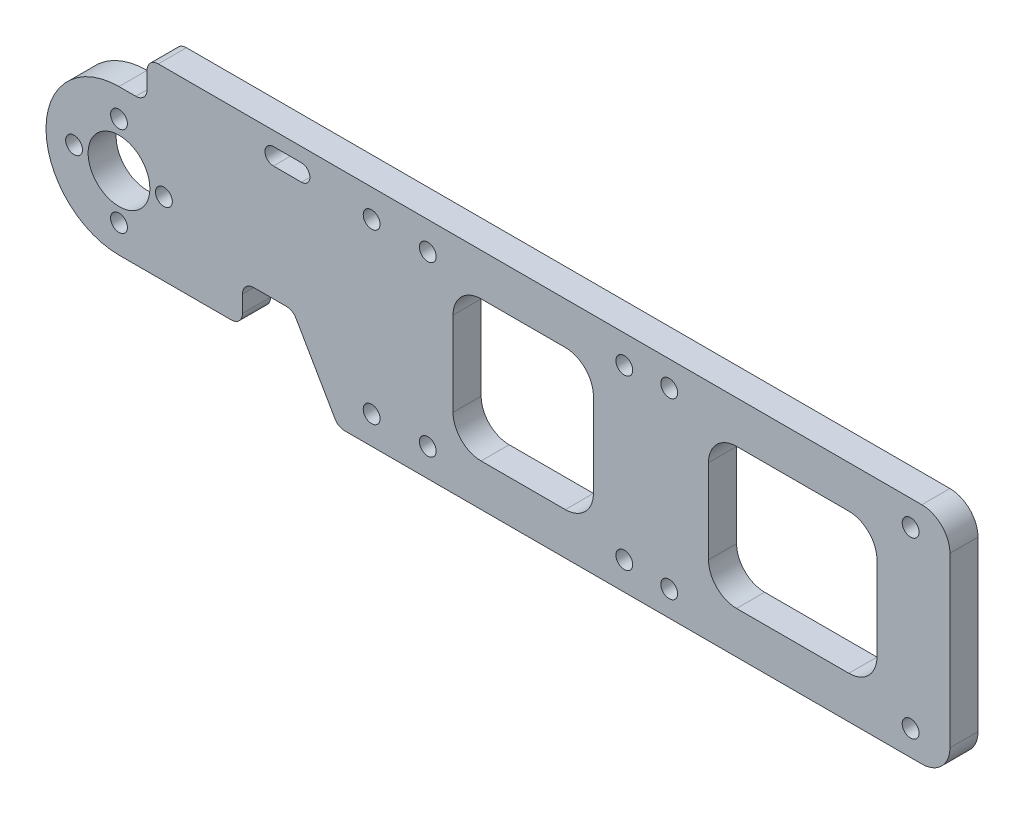
SolidWorks part; units mm, degrees
material "Acrylic (Medium-high impact)"
ref_plane "Front Plane" through (0, 0, 0) normal (0, 0, 1) x (1, 0, 0)
ref_plane "Top Plane" through (0, 0, 0) normal (0, 1, 0) x (1, 0, 0)
ref_plane "Right Plane" through (0, 0, 0) normal (1, 0, 0) x (0, 0, -1)
sketch "Sketch2" plane through (0, 0, 0) normal (0, 0, 1) x (1, 0, 0)
  line L0 (0, 20) -> (0, -20)
  line L1 (0, 20) -> (148, 20)
  line L2 (0, -20) -> (148, -20)
  line L3 (148, 20) -> (148, -20)
  line L4 (0, 0) -> (-17, 0)
  line L5 (0, -13) -> (35, -13)
  line L6 (35, -13) -> (35, -20)
  line L7 (5, 13) -> (22, -6)
  line L8 (0, 13) -> (5, 13)
  line L9 (0, 13) -> (0, 20)
  line L10 (0, 20) -> (5, 20)
  line L11 (5, 13) -> (5, 20)
  line L12 (35, -13) -> (39.0415, -20)
  line L13 (22, -13) -> (35, -13)
  line L14 (22, -13) -> (22, -6)
  line L15 (22, -6) -> (35, -6)
  line L16 (35, -13) -> (35, -6)
  line L17 (35, -13) -> (30.9585, -6)
  circle A1 centre (0, 0) radius 5.5
  circle A2 centre (0, 0) radius 13
  dimension "D1" = 148
  dimension "D3" = 11
  dimension "D6" = 26
  dimension "D2" = 165
  dimension "D4" = 40
  dimension "D5" = 20
  dimension "D7" = 35
  dimension "D8" = 22
  dimension "D9" = 7
  dimension "D10" = 5
  dimension "D11" = 60
  dimension "D12" = 60
extrude "Boss-Extrude1" add sketch "Sketch2" along normal mid plane 5 contours A2 L2 L3 L1 | A1 L4 A2 L0 | A1 L0 A2 L4 | A2 L5 | A2 L8 | L7 A2 L0 A1 | L7 A2 | L17 L16 L15 region at (6.1639, -0.1248, 0) region at (4.3258, 12.5044, 0) region at (-6.2113, 6.2113, 0) region at (83.3624, 1.0992, 0) region at (9.4178, 8.4264, 0) region at (-6.2113, -6.2113, 0) region at (15.1507, -7.4075, 0) region at (33.6528, -8.3333, 0)
fillet "Fillet1" radius 5 2 edges at (148, -20, 0) (148, 20, 0)
sketch "Sketch3" plane through (0, 0, -2.5) normal (0, 0, -1) x (-1, 0, 0)
  line L0 (-83, 0) -> (-119.5, 0)
  line L1 (-141, 0) -> (-98, 0)
  line L2 (-90, 15) -> (-90, 0)
  line L3 (-119.5, 0) -> (-148, 0)
  line L4 (-141, 0) -> (-141, 15.5)
  line L5 (-98, 0) -> (-98, 15.5)
  line L12 (0, 0) -> (0, 15.666)
  line L13 (0, 0) -> (-83, 0)
  line L14 (-32.5, 16) -> (-27.5, 16) construction
  line L17 (-32.5, 17.5) -> (-27.5, 17.5)
  line L18 (-32.5, 14.5) -> (-27.5, 14.5)
  line L19 (0, 0) -> (18.4819, 0)
  line L24 (-22, -6) -> (-22, -13)
  line L25 (-148, 15) -> (-148, -15)
  line L27 (-148, 15) -> (-148, -15)
  line L29 (-143, -20) -> (-39.0415, -20)
  line L31 (-143, -20) -> (-39.0415, -20)
  line L33 (-5, 20) -> (-143, 20)
  line L35 (-5, 20) -> (-143, 20)
  line L36 (-39.0415, -20) -> (-30.9585, -6)
  line L38 (-22, -13) -> (0, -13)
  line L39 (-22, -13) -> (0, -13)
  line L40 (0, 13) -> (-5, 13)
  line L41 (0, 13) -> (-5, 13)
  line L42 (-5, 13) -> (-5, 20)
  line L43 (-5, 13) -> (-5, 20)
  line L44 (-30.9585, -6) -> (-22, -6)
  line L45 (-30.9585, -6) -> (-22, -6)
  line L46 (-22, -6) -> (-22, -13)
  line L49 (-39.0415, -20) -> (-30.9585, -6)
  circle A3 centre (-55, -15) radius 1.5
  arc A4 (0, -13) -> (0, 13) centre (0, 0) ccw
  circle A12 centre (-90, -15) radius 1.5
  circle A13 centre (-45, -15) radius 1.5
  arc A21 (-32.5, 17.5) -> (-32.5, 14.5) centre (-32.5, 16) ccw
  arc A22 (-27.5, 14.5) -> (-27.5, 17.5) centre (-27.5, 16) ccw
  circle A24 centre (-90, 15) radius 1.5
  circle A26 centre (-45, 15) radius 1.5
  circle A27 centre (0, 0) radius 8
  circle A28 centre (0, -8) radius 1.5
  circle A29 centre (-8, 0) radius 1.5
  circle A30 centre (0, 8) radius 1.5
  circle A31 centre (8, 0) radius 1.5
  circle A32 centre (-55, 15) radius 1.5
  arc A33 (-148, -15) -> (-143, -20) centre (-143, -15) ccw
  arc A34 (-148, -15) -> (-143, -20) centre (-143, -15) ccw
  arc A35 (-143, 20) -> (-148, 15) centre (-143, 15) ccw
  arc A36 (-143, 20) -> (-148, 15) centre (-143, 15) ccw
  circle A37 centre (-141, 15.5) radius 1.5
  circle A38 centre (-98, 15.5) radius 1.5
  arc A42 (0, -13) -> (0, 13) centre (0, 0) ccw
  circle A43 centre (-141, -15.5) radius 1.5
  circle A44 centre (-98, -15.5) radius 1.5
  point P21 (0, 0)
  point P35 (-30, 16)
  point P48 (15.666, 0)
  point P53 (-12, 0)
  point P54 (-7.6279, -12)
  dimension "D6" = 51
  dimension "D10" = 15
  dimension "D11" = 16
  dimension "D13" = 45
  dimension "D17" = 3
  dimension "D18" = 4
  dimension "D12" = 3
  dimension "D19" = 16
  dimension "D21" = 3
  dimension "D22" = 3
  dimension "D5" = 3
  dimension "D24" = 3
  dimension "D3" = 43
  dimension "D4" = 15.5
  dimension "D7" = 15
  dimension "D8" = 15
  dimension "D9" = 30
  dimension "D14" = 5
  dimension "D15" = 3
  dimension "D16" = 16
  dimension "D20" = 35
  dimension "D23" = 15.5
  dimension "D1" = 0
extrude "Cut-Extrude1" cut sketch "Sketch3" against normal through all contours L18 A22 L17 A21 | A12 | A43 | A27 A28 | A27 A28 | L19 A31 A27 | A27 A31 L19 | L19 A31 A27 | A27 A31 L19 | A27 A29 L13 | L13 A29 A27 | A27 A29 L13 | L13 A29 A27 | A27 A30 L12 | L12 A30 A27 | A27 A30 L12 | L12 A30 A27 | A3 | A24 | A26 | A13 | A32 | A37 | A38 | A44 region at (142.0307, 16.5307, -2.5) region at (99.0307, 16.5307, -2.5) region at (91.0307, 16.0307, -2.5) region at (8.6106, 0.6553, -2.5) region at (8.6106, -0.6553, -2.5) region at (7.3387, 0.6164, -2.5) region at (7.3387, -0.6164, -2.5) region at (0.6553, 8.6106, -2.5) region at (0.6164, 7.3387, -2.5) region at (0, -7.3387, -2.5) region at (0, -8.6106, -2.5) region at (-0.6164, 7.3387, -2.5) region at (-0.6553, 8.6106, -2.5) region at (-7.3387, 0.6164, -2.5) region at (-7.3387, -0.6164, -2.5) region at (-8.6106, -0.6553, -2.5) region at (-8.6106, 0.6553, -2.5) region at (30, 16, -2.5) region at (55, -15, -2.5) region at (90, -15, -2.5) region at (45, -15, -2.5) region at (45, 15, -2.5) region at (55, 15, -2.5) region at (141, -15.5, -2.5) region at (98, -15.5, -2.5)
fillet "Fillet2" radius 2 6 edges at (5, 20, 0) (5, 13, 0) (22, -13, 0) (22, -6, 0) (39.0415, -20, 0) (30.9585, -6, 0)
sketch "Sketch4" plane through (0, 0, 2.5) normal (0, 0, 1) x (1, 0, 0)
  line L1 (55, 0) -> (148, 0)
  line L2 (90, 15) -> (90, -15)
  line L4 (84.5, -12.5) -> (59.5, -12.5)
  line L9 (31.5359, -7) -> (38.4641, -19)
  line L10 (40.1962, -20) -> (143, -20)
  line L11 (148, -15) -> (148, 15)
  line L12 (143, 20) -> (7, 20)
  line L13 (5, 18) -> (5, 15)
  line L14 (3, 13) -> (0, 13)
  line L15 (0, -13) -> (20, -13)
  line L16 (22, -11) -> (22, -8)
  line L17 (24, -6) -> (29.8038, -6)
  line L18 (31.5359, -7) -> (38.4641, -19)
  line L19 (40.1962, -20) -> (143, -20)
  line L20 (148, -15) -> (148, 15)
  line L21 (143, 20) -> (7, 20)
  line L22 (5, 18) -> (5, 15)
  line L23 (3, 13) -> (0, 13)
  line L24 (0, -13) -> (20, -13)
  line L25 (22, -11) -> (22, -8)
  line L26 (24, -6) -> (29.8038, -6)
  line L27 (84.5, -12.5) -> (84.5, 12.5)
  line L28 (84.5, 12.5) -> (59.5, 12.5)
  line L33 (59.5, -12.5) -> (59.5, 12.5)
  line L34 (84.5, -12.5) -> (59.5, 12.5) construction
  line L35 (84.5, 12.5) -> (59.5, -12.5) construction
  line L36 (105, 12.5) -> (135, 12.5)
  line L37 (105, 12.5) -> (105, -12.5)
  line L38 (105, -12.5) -> (135, -12.5)
  line L39 (135, 12.5) -> (135, -12.5)
  line L40 (105, 12.5) -> (135, -12.5) construction
  line L41 (105, -12.5) -> (135, 12.5) construction
  arc A9 (38.4641, -19) -> (40.1962, -20) centre (40.1962, -18) ccw
  arc A10 (143, -20) -> (148, -15) centre (143, -15) ccw
  arc A11 (148, 15) -> (143, 20) centre (143, 15) ccw
  arc A12 (7, 20) -> (5, 18) centre (7, 18) ccw
  arc A13 (3, 13) -> (5, 15) centre (3, 15) ccw
  arc A14 (0, 13) -> (0, -13) centre (0, 0) ccw
  arc A15 (20, -13) -> (22, -11) centre (20, -11) ccw
  arc A16 (24, -6) -> (22, -8) centre (24, -8) ccw
  arc A17 (31.5359, -7) -> (29.8038, -6) centre (29.8038, -8) ccw
  arc A18 (38.4641, -19) -> (40.1962, -20) centre (40.1962, -18) ccw
  arc A19 (143, -20) -> (148, -15) centre (143, -15) ccw
  arc A20 (148, 15) -> (143, 20) centre (143, 15) ccw
  arc A21 (7, 20) -> (5, 18) centre (7, 18) ccw
  arc A22 (3, 13) -> (5, 15) centre (3, 15) ccw
  arc A23 (0, 13) -> (0, -13) centre (0, 0) ccw
  arc A24 (20, -13) -> (22, -11) centre (20, -11) ccw
  arc A25 (24, -6) -> (22, -8) centre (24, -8) ccw
  arc A26 (31.5359, -7) -> (29.8038, -6) centre (29.8038, -8) ccw
  point P2 (0, 0)
  point P27 (72, 0)
  point P35 (120, 0)
  dimension "D2" = 18
  dimension "D3" = 30
  dimension "D4" = 25
  dimension "D5" = 25
  dimension "D6" = 25
  dimension "D7" = 30
  dimension "D1" = 0
extrude "Cut-Extrude2" cut sketch "Sketch4" against normal blind 10 contours L33 L1 L27 L28 | L33 L4 L27 L1 | L39 L36 L37 L1 | L39 L1 L37 L38 region at (72, 6.25, 2.5) region at (72, -6.25, 2.5) region at (120, 6.25, 2.5) region at (120, -6.25, 2.5)
fillet "Fillet3" radius 5 8 edges at (135, 12.5, 0) (105, 12.5, 0) (135, -12.5, 0) (105, -12.5, 0) (84.5, -12.5, 0) (84.5, 12.5, 0) (59.5, -12.5, 0) (59.5, 12.5, 0)
